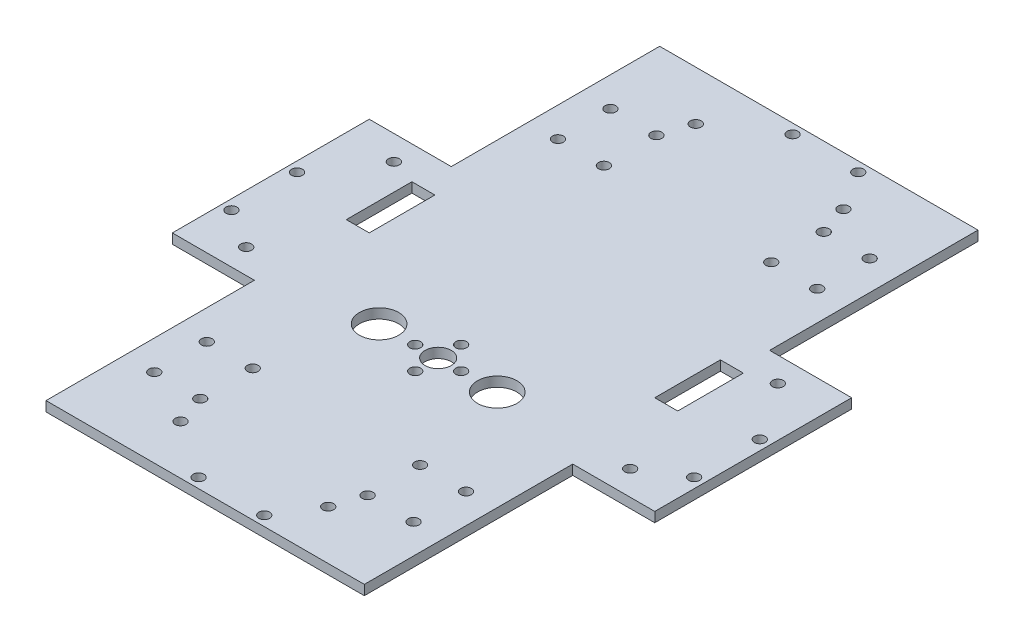
SolidWorks part; units mm, degrees
note: The reader was unsure of these and kept them because the rebuilt part matched: shared geometry of "草图3<4>".
ref_plane "前视基准面" through (0, 0, 0) normal (0, 0, 1) x (1, 0, 0)
ref_plane "上视基准面" through (0, 0, 0) normal (0, 1, 0) x (1, 0, 0)
ref_plane "右视基准面" through (0, 0, 0) normal (1, 0, 0) x (0, 0, -1)
other "Configuration Table"
sketch "草图1" plane through (0, 0, 0) normal (0, 1, 0) x (1, 0, 0)
  line L1 (-48.5, -93.5) -> (48.5, -93.5)
  line L2 (-48.5, -93.5) -> (-48.5, 93.5)
  line L3 (-48.5, 93.5) -> (48.5, 93.5)
  line L4 (48.5, -93.5) -> (48.5, 93.5)
  line L5 (-48.5, -93.5) -> (48.5, 93.5) construction
  line L6 (-48.5, 93.5) -> (48.5, -93.5) construction
  point P0 (0, 0)
  dimension "D1" = 187
  dimension "D2" = 97
extrude "凸台-拉伸1" add sketch "草图1" along normal blind 3
sketch "草图2" plane through (0, 3, 0) normal (0, 1, 0) x (1, 0, 0)
  line L0 (0, 132.1478) -> (0, -132.1478) construction
  line L1 (-48.5, -93.5) -> (48.5, -93.5) construction
  line L6 (25.5, -69.5) -> (39.5, -69.5) construction
  line L7 (25.5, -69.5) -> (25.5, -53.5) construction
  line L8 (25.5, -53.5) -> (39.5, -53.5) construction
  line L9 (39.5, -69.5) -> (39.5, -53.5) construction
  line L10 (25.5, -69.5) -> (39.5, -53.5) construction
  line L11 (25.5, -53.5) -> (39.5, -69.5) construction
  line L13 (48.5, -93.5) -> (48.5, 93.5) construction
  line L14 (32.5, -61.5) -> (68.0132, -61.5) construction
  line L15 (-32.5, -61.5) -> (-68.0132, -61.5) construction
  line L16 (-25.5, -53.5) -> (-39.5, -69.5) construction
  line L17 (-25.5, -69.5) -> (-39.5, -53.5) construction
  line L18 (-39.5, -69.5) -> (-39.5, -53.5) construction
  line L19 (-25.5, -53.5) -> (-39.5, -53.5) construction
  line L20 (-25.5, -69.5) -> (-25.5, -53.5) construction
  line L21 (-25.5, -69.5) -> (-39.5, -69.5) construction
  line L22 (0, 0) -> (77.8965, 0) construction
  line L23 (-25.5, 69.5) -> (-39.5, 69.5) construction
  line L24 (-25.5, 69.5) -> (-25.5, 53.5) construction
  line L25 (-25.5, 53.5) -> (-39.5, 53.5) construction
  line L26 (-39.5, 69.5) -> (-39.5, 53.5) construction
  line L27 (-25.5, 69.5) -> (-39.5, 53.5) construction
  line L28 (-25.5, 53.5) -> (-39.5, 69.5) construction
  line L29 (-32.5, 61.5) -> (-68.0132, 61.5) construction
  line L30 (32.5, 61.5) -> (68.0132, 61.5) construction
  line L31 (25.5, 53.5) -> (39.5, 69.5) construction
  line L32 (25.5, 69.5) -> (39.5, 53.5) construction
  line L33 (39.5, 69.5) -> (39.5, 53.5) construction
  line L34 (25.5, 53.5) -> (39.5, 53.5) construction
  line L35 (25.5, 69.5) -> (25.5, 53.5) construction
  line L36 (25.5, 69.5) -> (39.5, 69.5) construction
  circle A0 centre (39.5, -53.5) radius 1.65
  circle A1 centre (25.5, -53.5) radius 1.65
  circle A2 centre (25.5, -69.5) radius 1.65
  circle A3 centre (39.5, -69.5) radius 1.65
  circle A4 centre (-39.5, -69.5) radius 1.65
  circle A5 centre (-25.5, -69.5) radius 1.65
  circle A6 centre (-25.5, -53.5) radius 1.65
  circle A7 centre (-39.5, -53.5) radius 1.65
  circle A8 centre (-39.5, 53.5) radius 1.65
  circle A9 centre (-25.5, 53.5) radius 1.65
  circle A10 centre (-25.5, 69.5) radius 1.65
  circle A11 centre (-39.5, 69.5) radius 1.65
  circle A12 centre (39.5, 69.5) radius 1.65
  circle A13 centre (25.5, 69.5) radius 1.65
  circle A14 centre (25.5, 53.5) radius 1.65
  circle A15 centre (39.5, 53.5) radius 1.65
  point P3 (0, -64.0751)
  point P4 (32.5, -61.5)
  point P29 (-32.5, -61.5)
  point P52 (-32.5, 61.5)
  point P53 (32.5, 61.5)
  point P54 (0, 64.0751)
  dimension "D5" = 3.3
  dimension "D6" = 3.3
  dimension "D1" = 16
  dimension "D2" = 14
  dimension "D3" = 32
  dimension "D4" = 9
extrude "切除-拉伸1" cut sketch "草图2" against normal blind 3
sketch "草图3" plane through (0, 3, 0) normal (0, 1, 0) x (1, 0, 0)
  line L0 (-80.5065, 0) -> (65.6654, 0) construction
  line L1 (0, -50.0456) -> (0, 28.8555) construction
  line L2 (27.5, -35) -> (-27.5, -35)
  line L3 (27.5, -35) -> (27.5, -10)
  line L4 (27.5, -10) -> (-27.5, -10)
  line L5 (-27.5, -35) -> (-27.5, -10)
  line L6 (27.5, -35) -> (-27.5, -10) construction
  line L7 (27.5, -10) -> (-27.5, -35) construction
  line L8 (36.6157, -22.5) -> (-34.0088, -22.5) construction
  circle A0 centre (0, -22.5) radius 7 construction
  circle A2 centre (0, -22.5) radius 4
  circle A3 centre (-18.5, -22.5) radius 1.65
  circle A4 centre (-7, -22.5) radius 1.65
  circle A5 centre (18.5, -22.5) radius 1.65
  point P3 (0, -22.5)
  dimension "D3" = 14
  dimension "D4" = 8
  dimension "D5" = 3.3
  dimension "D6" = 3.3
  dimension "D1" = 25
  dimension "D2" = 55
  dimension "D7" = 37
  dimension "D8" = 10
extrude "切除-拉伸2" cut sketch "草图3" against normal blind 3 contours A5 | A3 | A2
extrude "切除-拉伸3" cut sketch "草图3<4>" against normal blind 3 contours A4
sketch "草图3<4>" plane through (0, 3, 0) normal (0, 1, 0) x (1, 0, 0) same geometry as "草图3"
pattern_circular "阵列(圆周)1" count 4 over 360 about axis through (0, 0, 22.5) along (0, 1, 0) of "切除-拉伸3"
sketch "草图4" plane through (0, 3, 0) normal (0, 1, 0) x (1, 0, 0)
  line L0 (0, 113.5228) -> (0, -115.4587) construction
  line L1 (-70.0311, 0) -> (75.7272, 0) construction
  line L2 (48.5, -93.5) -> (48.5, 93.5) construction
  line L3 (48.5, -30) -> (73.5, -30)
  line L4 (48.5, -30) -> (48.5, 30)
  line L5 (48.5, 30) -> (73.5, 30)
  line L6 (73.5, -30) -> (73.5, 30)
  line L7 (48.5, -30) -> (73.5, 30) construction
  line L8 (48.5, 30) -> (73.5, -30) construction
  point P5 (61, 0)
  dimension "D1" = 60
  dimension "D2" = 25
extrude "凸台-拉伸2" add sketch "草图4" against normal blind 3
mirror "镜向1" about plane through (0, 0, 0) normal (1, 0, 0) of "凸台-拉伸2"
sketch "草图5" plane through (0, 3, 0) normal (0, 1, 0) x (1, 0, 0)
  line L0 (0, 0) -> (101.5368, 0) construction
  line L1 (48.5, 30) -> (48.5, 93.5) construction
  circle A0 centre (55.5, 22.5) radius 1.65
  circle A1 centre (55.5, -22.5) radius 1.65
  dimension "D1" = 3.3
  dimension "D2" = 7
  dimension "D3" = 45
extrude "切除-拉伸4" [suppressed] cut sketch "草图5" against normal blind 3
mirror "镜向2" [suppressed] about plane through (0, 0, 0) normal (1, 0, 0)
extrude "切除-拉伸5" cut sketch "草图6" against normal blind 3
sketch "草图6" plane through (0, 0, 0) normal (0, -1, 0) x (1, 0, 0)
  circle A2 centre (-5, 90.5) radius 1.65
  circle A3 centre (15, 90.5) radius 1.65
  circle A6 centre (-5, -90.5) radius 1.65
  circle A7 centre (15, -90.5) radius 1.65
extrude "切除-拉伸6" cut sketch "草图7" against normal blind 3
sketch "草图7" plane through (0, 3, 0) normal (0, 1, 0) x (1, 0, 0)
  circle A2 centre (22.5, 78.5) radius 1.65
  circle A3 centre (-22.5, 78.5) radius 1.65
  circle A6 centre (22.5, -78.5) radius 1.65
  circle A7 centre (-22.5, -78.5) radius 1.65
  circle A12 centre (53.5, -22.5) radius 1.65
  circle A13 centre (53.5, 22.5) radius 1.65
  circle A14 centre (-53.5, 22.5) radius 1.65
  circle A15 centre (-53.5, -22.5) radius 1.65
extrude "切除-拉伸7" [suppressed] cut sketch "草图8" against normal blind 3
sketch "草图8" plane through (0, 0, 0) normal (0, -1, 0) x (1, 0, 0)
  circle A2 centre (67.5, -8) radius 1.65
  circle A3 centre (67.5, 12) radius 1.65
  circle A6 centre (-67.5, -8) radius 1.65
  circle A7 centre (-67.5, 12) radius 1.65
extrude "切除-拉伸8" cut sketch "草图9" against normal up to next
sketch "草图9" plane through (0, 3, 0) normal (0, 1, 0) x (1, 0, 0)
  circle A2 centre (-18, -22.5) radius 6
  circle A3 centre (18, -22.5) radius 6
extrude "切除-拉伸15" cut sketch "草图24" against normal up to surface (3 mm away) up to face at (-18, 0, 16.5)
sketch "草图24" plane through (0, 3, 0) normal (0, 1, 0) x (1, 0, 0)
  circle A8 centre (-22.5, -78.5) radius 1.65
  circle A9 centre (22.5, -78.5) radius 1.65
  circle A10 centre (22.5, 78.5) radius 1.65
  circle A11 centre (-22.5, 78.5) radius 1.65
  circle A12 centre (-100.1515, -27.458) radius 1.65
  circle A13 centre (-95.4063, 17.2911) radius 1.65
  circle A14 centre (58.5, -22.5) radius 1.65
  circle A15 centre (58.5, 22.5) radius 1.65
extrude "切除-拉伸11" [suppressed] cut sketch "草图12" against normal blind 3
sketch "草图12" [suppressed] plane through (0, 3, 0) normal (0, 1, 0) x (1, 0, 0)
  circle A2 centre (22.5, 78.5) radius 1.65
  circle A3 centre (-22.5, 78.5) radius 1.65
  circle A12 centre (53.5, -22.5) radius 1.65
  circle A17 centre (-53.5, -22.5) radius 1.65
extrude "切除-拉伸24" cut sketch "草图33" against normal up to surface (3 mm away) up to face at (22.5, 3, 80.15)
sketch "草图33" plane through (0, 0, 0) normal (0, -1, 0) x (1, 0, 0)
  circle A2 centre (70.5, -5) radius 1.65
  circle A3 centre (70.5, 15) radius 1.65
  circle A6 centre (-70.5, -5) radius 1.65
  circle A7 centre (-70.5, 15) radius 1.65
sketch "草图42" plane through (0, 3, 0) normal (0, 1, 0) x (1, 0, 0)
  circle A0 centre (-58.5, 22.5) radius 1.65 construction
  circle A1 centre (-58.5, -22.5) radius 1.65 construction
  circle A2 centre (-58.5, 22.5) radius 1.65
  circle A3 centre (-58.5, -22.5) radius 1.65
extrude "切除-拉伸32" cut sketch "草图42" against normal up to surface (3 mm away) up to face at (70.5, 0, 13.35)
sketch "草图44" plane through (0, 3, 0) normal (0, 1, 0) x (1, 0, 0)
  line L0 (0, 0) -> (0, 123.51) construction
  line L1 (-50.5, 0) -> (-43.5, 0)
  line L2 (-50.5, 0) -> (-50.5, 20)
  line L3 (-50.5, 20) -> (-43.5, 20)
  line L4 (-43.5, 0) -> (-43.5, 20)
  line L5 (-50.5, 0) -> (-43.5, 20) construction
  line L6 (-50.5, 20) -> (-43.5, 0) construction
  line L8 (37, -10) -> (-37, -10) construction
  line L9 (50.5, 20) -> (43.5, 0) construction
  line L10 (50.5, 0) -> (43.5, 20) construction
  line L11 (43.5, 0) -> (43.5, 20)
  line L12 (50.5, 20) -> (43.5, 20)
  line L13 (50.5, 0) -> (50.5, 20)
  line L14 (50.5, 0) -> (43.5, 0)
  line L15 (-48.5, 93.5) -> (-48.5, 30) construction
  point P0 (-47, 10)
  point P16 (47, 10)
  dimension "D1" = 7
  dimension "D2" = 2
  dimension "D3" = 20
  dimension "D4" = 10
extrude "切除-拉伸34" cut sketch "草图44" against normal blind 10
